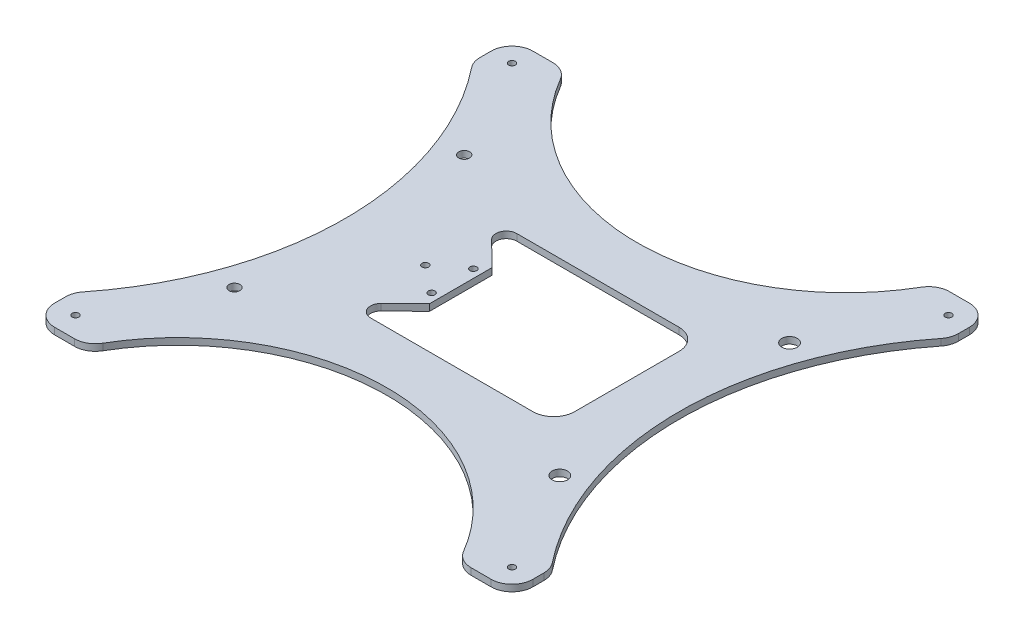
SolidWorks part; units mm, degrees
material "6061-T6 (SS)"
ref_plane "Front Plane" through (0, 0, 0) normal (0, 0, 1) x (1, 0, 0)
ref_plane "Top Plane" through (0, 0, 0) normal (0, 1, 0) x (1, 0, 0)
ref_plane "Right Plane" through (0, 0, 0) normal (1, 0, 0) x (0, 0, -1)
sketch "Sketch1" plane through (0, 0, 0) normal (0, 1, 0) x (1, 0, 0)
  line L0 (-114.5, 114.5) -> (-114.5, 95.7066)
  line L1 (-114.5, -114.5) -> (-114.5, -95.7066)
  line L2 (114.5, 114.5) -> (89.0491, 114.5)
  line L3 (114.5, 114.5) -> (-114.5, 114.5) construction
  line L4 (-114.5, 114.5) -> (-89.0491, 114.5)
  line L5 (55, 35) -> (-55, 35)
  line L6 (55, 35) -> (55, -35)
  line L7 (55, -35) -> (-55, -35)
  line L8 (-55, 35) -> (-55, -35)
  line L9 (55, 35) -> (-55, -35) construction
  line L10 (0, -114.5) -> (0, 114.5) construction
  line L11 (0, 0) -> (-114.5, 0) construction
  line L12 (55, -35) -> (-55, 35) construction
  line L13 (114.5, 114.5) -> (114.5, -114.5) construction
  line L14 (114.5, -114.5) -> (-114.5, -114.5) construction
  line L15 (-114.5, 114.5) -> (-114.5, -114.5) construction
  line L16 (114.5, 114.5) -> (-114.5, -114.5) construction
  line L17 (114.5, -114.5) -> (-114.5, 114.5) construction
  line L18 (114.5, -114.5) -> (114.5, -95.7066)
  line L19 (114.5, 114.5) -> (114.5, 95.7066)
  line L20 (114.5, -114.5) -> (89.0491, -114.5)
  line L21 (-114.5, -114.5) -> (-89.0491, -114.5)
  circle A0 centre (77.9, 55) radius 3.7
  circle A1 centre (-10, 50) radius 1.6
  circle A2 centre (-104.5, 104.5) radius 1.6
  circle A3 centre (-5, 60) radius 1.6
  circle A4 centre (77.9, -55) radius 3.7
  circle A5 centre (-77.9, 55) radius 2.6
  arc A6 (-89.0491, 114.5) -> (-14.7916, 61.1) centre (0, 160) ccw
  arc A7 (-89.0491, -114.5) -> (-14.7916, -61.1) centre (0, -160) cw
  circle A8 centre (-104.5, -104.5) radius 1.6
  arc A9 (-114.5, -95.7066) -> (-114.5, 95.7066) centre (-230, 0) ccw
  circle A10 centre (-77.9, -55) radius 2.6
  circle A11 centre (-10, -50) radius 1.6
  circle A12 centre (-5, -60) radius 1.6
  circle A13 centre (104.5, -104.5) radius 1.6
  circle A14 centre (77.9, -55) radius 2.6 construction
  circle A15 centre (5, -60) radius 1.6
  circle A16 centre (10, -50) radius 1.6
  circle A17 centre (104.5, 104.5) radius 1.6
  circle A18 centre (77.9, 55) radius 2.6 construction
  circle A19 centre (10, 50) radius 1.6
  circle A20 centre (5, 60) radius 1.6
  arc A21 (114.5, -95.7066) -> (114.5, 95.7066) centre (230, 0) cw
  arc A22 (14.7916, -61.1) -> (-14.7916, -61.1) centre (0, -35) cw
  arc A23 (14.7916, 61.1) -> (-14.7916, 61.1) centre (0, 35) ccw
  arc A24 (14.7916, 61.1) -> (89.0491, 114.5) centre (0, 160) ccw
  arc A25 (14.7916, -61.1) -> (89.0491, -114.5) centre (0, -160) cw
  point P2 (0, 114.5)
  point P21 (0, 60)
  point P26 (-80, 0)
  point P62 (0, 0)
  point P80 (0, 0)
  dimension "D2" = 155.8
  dimension "D3" = 110
  dimension "D6" = 10
  dimension "D7" = 5.2
  dimension "D9" = 10
  dimension "D11" = 10
  dimension "D12" = 20
  dimension "D14" = 3.2
  dimension "D15" = 25
  dimension "D8" = 10
  dimension "D13" = 209
  dimension "D17" = 7.4
  dimension "D16" = 100
  dimension "D18" = 25
  dimension "D19" = 150
  dimension "D20" = 30
  dimension "D4" = 110
  dimension "D5" = 70
  dimension "D10" = 50
extrude "Boss-Extrude1" add sketch "Sketch1" along normal blind 3.175
fillet "Fillet1" radius 10 20 edges at (-114.5, 1.5875, -114.5) (55, 1.5875, 35) (55, 1.5875, -35) (-55, 1.5875, 35) (-55, 1.5875, -35) (114.5, 1.5875, 114.5) (114.5, 1.5875, 95.7066) (114.5, 1.5875, -95.7066) (114.5, 1.5875, -114.5) (-89.0491, 1.5875, -114.5) (-114.5, 1.5875, -95.7066) (-114.5, 1.5875, 95.7066) (-89.0491, 1.5875, 114.5) (-114.5, 1.5875, 114.5) (-14.7916, 1.5875, 61.1) (14.7916, 1.5875, 61.1) (-14.7916, 1.5875, -61.1) (14.7916, 1.5875, -61.1) (89.0491, 1.5875, -114.5) (89.0491, 1.5875, 114.5)
sketch "Sketch2" plane through (0, 3.175, 0) normal (0, 1, 0) x (1, 0, 0)
  line L0 (-77.9, 55) -> (-77.9, -55) construction
ref_plane "Plane1" through (-77.9, 0, 0) normal (-1, 0, 0) x (0, 0, 1)
sketch "Sketch3" plane through (0, 3.175, 0) normal (0, 1, 0) x (1, 0, 0)
  line L0 (-86.3385, -109.5455) -> (86.3385, -109.5455)
  line L1 (-86.3385, 109.5455) -> (86.3385, 109.5455)
  circle A0 centre (10, 50) radius 1.6 construction
  circle A1 centre (5, 60) radius 1.6 construction
  circle A2 centre (-5, 60) radius 1.6 construction
  circle A3 centre (-10, 50) radius 1.6 construction
  arc A4 (18.1812, 61.6667) -> (86.3385, 109.5455) centre (0, 160) ccw construction
  arc A5 (-86.3385, 109.5455) -> (-18.1812, 61.6667) centre (0, 160) ccw construction
  arc A6 (86.3385, -109.5455) -> (18.1812, -61.6667) centre (0, -160) ccw construction
  arc A7 (-18.1812, -61.6667) -> (-86.3385, -109.5455) centre (0, -160) ccw construction
  circle A8 centre (-10, -50) radius 1.6 construction
  circle A9 centre (10, -50) radius 1.6 construction
  circle A10 centre (5, -60) radius 1.6 construction
  circle A11 centre (-5, -60) radius 1.6 construction
  circle A12 centre (10, 50) radius 1.6
  circle A13 centre (5, 60) radius 1.6
  circle A14 centre (-5, 60) radius 1.6
  circle A15 centre (-10, 50) radius 1.6
  arc A16 (18.1812, 61.6667) -> (86.3385, 109.5455) centre (0, 160) ccw
  arc A17 (-86.3385, 109.5455) -> (18.1812, 61.6667) centre (0, 160) ccw
  arc A18 (86.3385, -109.5455) -> (18.1812, -61.6667) centre (0, -160) ccw
  arc A19 (18.1812, -61.6667) -> (-86.3385, -109.5455) centre (0, -160) ccw
  circle A20 centre (-10, -50) radius 1.6
  circle A21 centre (10, -50) radius 1.6
  circle A22 centre (5, -60) radius 1.6
  circle A23 centre (-5, -60) radius 1.6
extrude "Cut-Extrude1" cut sketch "Sketch3" against normal up to surface (3.175 mm away) contours A17 A16 L1 | A19 L0 A18 up to face at (10, 0, -51.6)
extrude "Boss-Extrude2" add sketch "Sketch3<3>" against normal up to surface (3.175 mm away) contours A19 A23 | A19 A22 | A17 A13 | A17 A14 | A15 | A12 | A20 | A21 region at (-5.0305, 3.175, 59.3909) region at (5.0305, 3.175, 59.3909) region at (-5.0305, 3.175, -59.3909) region at (5.0305, 3.175, -59.3909) up to face at (0, 0, 0)
sketch "Sketch3<3>" plane through (0, 3.175, 0) normal (0, 1, 0) x (1, 0, 0) same geometry as "Sketch3"
sketch "Sketch4" plane through (0, 3.175, 0) normal (0, 1, 0) x (1, 0, 0)
  line L0 (0, 0) -> (-28.5, 0) construction
  line L1 (-28.5, 10) -> (-28.5, -10) construction
  line L2 (-24.5, -15) -> (-24.5, 15)
  line L3 (-24.5, 15) -> (-45, 35)
  line L4 (-24.5, -15) -> (-45, -35)
  line L5 (-55, 25) -> (-55, -25) construction
  line L6 (-55, 25) -> (-55, -25)
  line L7 (-28.5, 0) -> (-41.5, 0) construction
  circle A0 centre (-28.5, 10) radius 1.6
  circle A1 centre (-28.5, -10) radius 1.6
  arc A2 (-45, 35) -> (-55, 25) centre (-45, 25) ccw construction
  arc A3 (-55, -25) -> (-45, -35) centre (-45, -25) ccw construction
  arc A4 (-45, 35) -> (-55, 25) centre (-45, 25) ccw
  arc A5 (-55, -25) -> (-45, -35) centre (-45, -25) ccw
  circle A6 centre (-41.5, 0) radius 1.6
  point P5 (-28.5, 0)
  point P15 (-24.5, 0)
  dimension "D3" = 3.2
  dimension "D1" = 28.5
  dimension "D2" = 20
  dimension "D4" = 15
  dimension "D5" = 4
  dimension "D6" = 13
extrude "Boss-Extrude3" add sketch "Sketch4" against normal up to surface (3.175 mm away) up to face at (0, 0, 0)
fillet "Fillet2" radius 5 2 edges at (-45, 1.5875, 35) (-45, 1.5875, -35)
